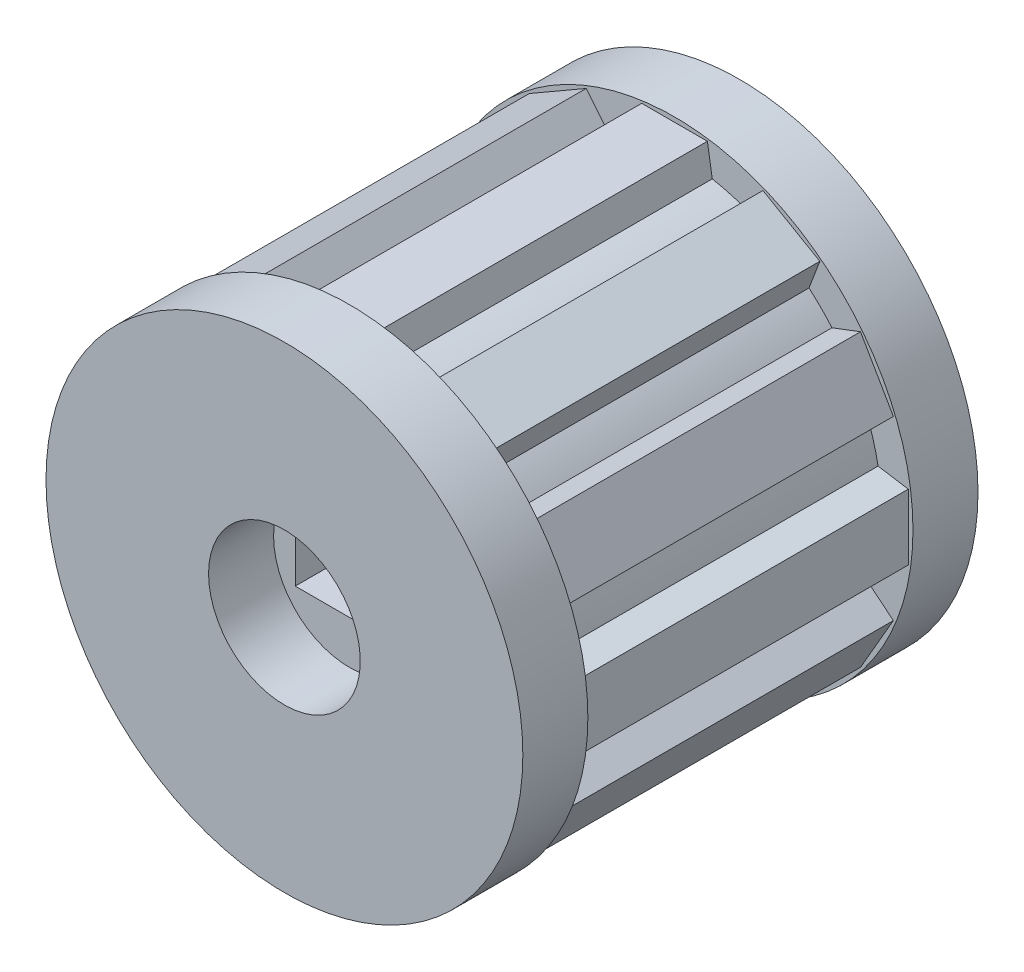
SolidWorks part; units mm, degrees
ref_plane "Plan de face" through (0, 0, 0) normal (0, 0, 1) x (1, 0, 0)
ref_plane "Plan de dessus" through (0, 0, 0) normal (0, 1, 0) x (1, 0, 0)
ref_plane "Plan de droite" through (0, 0, 0) normal (1, 0, 0) x (0, 0, -1)
sketch "Esquisse1" plane through (0, 0, 0) normal (0, 0, 1) x (1, 0, 0)
  line L0 (-2.5, 1.5) -> (2.5, 1.5)
  line L1 (-2.5, 1.5) -> (-2.5, -1.5)
  line L2 (-2.5, -1.5) -> (2.5, -1.5)
  line L3 (2.5, 1.5) -> (2.5, -1.5)
  circle A0 centre (0, 0) radius 11
  circle A1 centre (0, 0) radius 3.5
  point P7 (0, 1.5)
  point P8 (-2.5, 0)
  dimension "D1" = 22
  dimension "D2" = 5
  dimension "D3" = 3
extrude "Boss.-Extru.1" add sketch "Esquisse1" along normal blind 21 contours A0 A1 region at (-10.6889, 0, 0)
sketch "Esquisse2" plane through (0, 0, 0) normal (1, 0, 0) x (0, 0, -1)
  line L0 (0, 0) -> (-44, 0) construction
  line L1 (0, 0) -> (-22, 0)
  line L2 (-22, 0) -> (-22, 3.5)
  line L4 (-22, 3.5) -> (0, 3.5)
  line L6 (0, 3.5) -> (0, 0)
  dimension "D1" = 0
  dimension "D2" = 3.5
revolve "Enlèvement de matière-Révolution1" [suppressed] cut sketch "Esquisse2" angle 360 about L0
ref_plane "Plan1" through (0, 0, 3) normal (0, 0, -1) x (-1, 0, 0)
sketch "Esquisse3" plane through (0, 0, 3) normal (0, 0, -1) x (-1, 0, 0)
  circle A0 centre (0, 0) radius 9.55
  circle A1 centre (0, 0) radius 28.5
  dimension "D1" = 19.1
extrude "Enlèv. mat.-Extru.1" cut sketch "Esquisse3" against normal blind 15
sketch "Esquisse5" plane through (0, 0, 3) normal (0, 0, 1) x (1, 0, 0)
  line L0 (0, 0) -> (0, 38.7923) construction
  line L1 (0, 38.7923) -> (-15.821, 9.55) construction
  line L2 (-15.821, 9.55) -> (15.2424, 9.55) construction
  line L3 (0, 0) -> (-3.1054, 16.7555) construction
  line L7 (-1.7403, 9.3901) -> (-1.5153, 10.7822)
  line L8 (-1.5153, 10.7822) -> (1.5153, 10.7822)
  line L9 (0, 0) -> (3.1059, 16.758) construction
  line L10 (1.5153, 10.7822) -> (1.7403, 9.3901)
  line L11 (0, 0) -> (-1.8224, 12.9667) construction
  line L12 (0, 0) -> (1.8058, 12.8491) construction
  circle A0 centre (0, 0) radius 9.55 construction
  arc A1 (-1.7403, 9.3901) -> (1.7403, 9.3901) centre (0, 0) cw
  point P7 (0, 0)
  point P14 (0, 0)
  dimension "D5" = 10.5
  dimension "D6" = 10.5
  dimension "D7" = 9.55
  dimension "D1" = 3.0307
  dimension "D2" = 8
  dimension "D3" = 8
  dimension "D4" = 1.3921
extrude "Boss.-Extru.2" add sketch "Esquisse5" along normal up to surface (15 mm away) up to face at (-9.55, 0, 18)
pattern_circular "Répétition circulaire1" count 12 over 360 about axis through (0, 0, 3) along (0, 0, -1) of "Boss.-Extru.2"
extrude "Boss-Extrude1" add sketch "Esquisse1<3>" along normal mid plane 15 from offset 10.5 contours A1 L0 L3 L2 L1 region at (-3.401, 0, 0)
sketch "Esquisse1<3>" plane through (0, 0, 0) normal (0, 0, 1) x (1, 0, 0) same geometry as "Esquisse1"
sketch "Sketch1" plane through (0, 0, 3) normal (0, 0, 1) x (1, 0, 0)
  line L0 (9.1051, 2.8809) -> (9.3257, -2.0576)
  line L1 (7.2619, -6.2022) -> (6.2022, -7.2619)
  line L4 (10.0953, -4.0788) -> (8.58, -6.7034)
  arc A0 (9.1051, 2.8809) -> (9.3257, -2.0576) centre (0, 0) cw
  arc A1 (9.7272, -1.5461) -> (9.3257, -2.0576) centre (10.0581, -2.2192) ccw construction
  dimension "D1" = 4.9385
  dimension "D2" = 1.4986
  dimension "D3" = 3.0307
sketch "Sketch2" plane through (0, 0, 3) normal (0, 0, 1) x (1, 0, 0)
  line L0 (10.69, 1.3) -> (9.4315, 1.5) construction
  line L1 (8.5992, -6.4857) -> (9.9078, -4.2192) construction
  arc A0 (8.9179, 3.4167) -> (9.4315, 1.5) centre (0, 0) cw
  arc A1 (9.9078, -4.2192) -> (8.6078, -6.4708) centre (0, 0) cw
  dimension "D1" = 1.9843
  dimension "D2" = 10.7688
